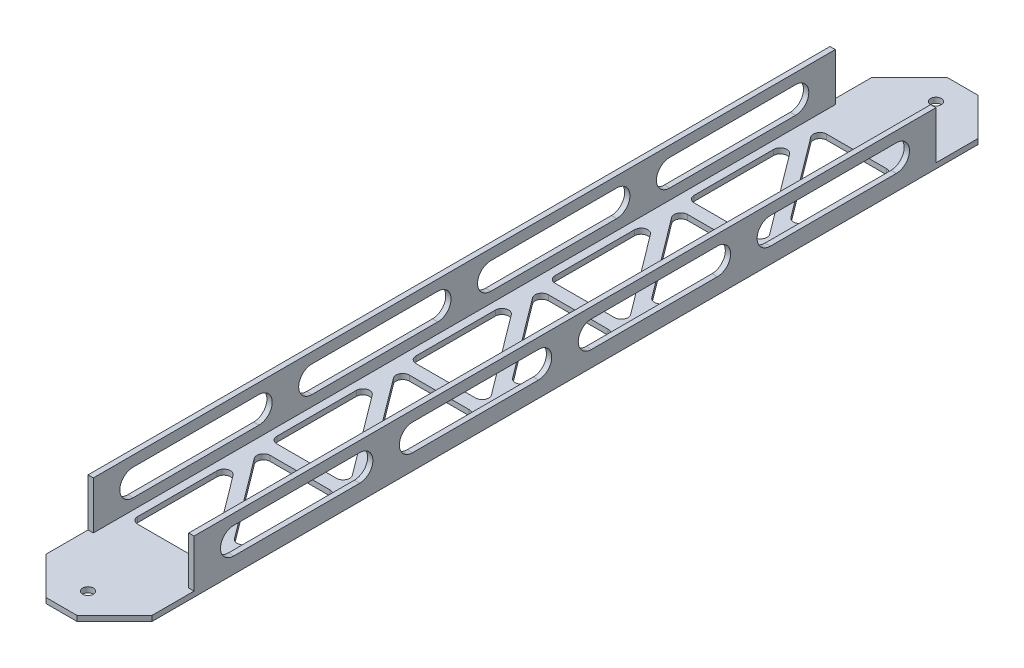
SolidWorks part; units mm, degrees
material "6061 Alloy"
ref_plane "Front" through (0, 0, 0) normal (0, 0, 1) x (1, 0, 0)
ref_plane "Top" through (0, 0, 0) normal (0, 1, 0) x (1, 0, 0)
ref_plane "Right" through (0, 0, 0) normal (1, 0, 0) x (0, 0, -1)
sketch "Sketch1" plane through (0, 0, 0) normal (0, 0, 1) x (1, 0, 0)
  line L0 (48.26, 2.54) -> (48.26, 25.4)
  line L1 (0, 0) -> (50.8, 0)
  line L2 (0, 0) -> (0, 25.4)
  line L4 (50.8, 0) -> (50.8, 25.4)
  line L5 (2.54, 2.54) -> (48.26, 2.54)
  line L6 (2.54, 2.54) -> (2.54, 25.4)
  line L7 (50.8, 25.4) -> (48.26, 25.4)
  line L8 (0, 25.4) -> (2.54, 25.4)
  dimension "D1" = 25.4
  dimension "D2" = 50.8
  dimension "D3" = 2.54
extrude "Boss-Extrude1" add sketch "Sketch1" along normal blind 431.8
sketch "Sketch2" plane through (0, 25.4, 0) normal (0, 1, 0) x (1, 0, 0)
  line L0 (50.8, -431.8) -> (50.8, 0) construction
  line L1 (0, -431.8) -> (50.8, -431.8)
  line L2 (0, -431.8) -> (0, -393.7)
  line L3 (0, -393.7) -> (50.8, -393.7)
  line L4 (50.8, -431.8) -> (50.8, -393.7)
  line L5 (0, -431.8) -> (50.8, -393.7) construction
  line L6 (0, -393.7) -> (50.8, -431.8) construction
  line L7 (0, -215.9) -> (50.8, -215.9) construction
  line L8 (0, -431.8) -> (0, 0) construction
  line L9 (0, -38.1) -> (50.8, 0) construction
  line L10 (0, 0) -> (50.8, -38.1) construction
  line L11 (50.8, 0) -> (50.8, -38.1)
  line L12 (0, -38.1) -> (50.8, -38.1)
  line L13 (0, 0) -> (0, -38.1)
  line L14 (0, 0) -> (50.8, 0)
  point P4 (25.4, -412.75)
  point P16 (25.4, -19.05)
  dimension "D1" = 38.1
extrude "Tabs" cut sketch "Sketch2" against normal up to surface (22.86 mm away) up to face at (25.4, 2.54, 215.9)
sketch "Sketch3" plane through (0, 2.54, 0) normal (0, 1, 0) x (1, 0, 0)
  line L0 (25.4, -431.8) -> (25.4, -419.1) construction
  line L1 (50.8, -431.8) -> (0, -431.8) construction
  line L2 (25.4, 0) -> (25.4, -12.7) construction
  line L3 (50.8, 0) -> (0, 0) construction
  circle A0 centre (25.4, -419.1) radius 2.5797
  circle A1 centre (25.4, -12.7) radius 2.5797
  dimension "D2" = 5.1594
  dimension "D1" = 12.7
extrude "Holes" cut sketch "Sketch3" against normal up to next
sketch "Sketch4" plane through (50.8, 0, 0) normal (1, 0, 0) x (0, 0, -1)
  line L0 (-57.15, 13.97) -> (-117.475, 13.97) construction
  line L1 (-57.15, 7.62) -> (-117.475, 7.62)
  line L2 (-57.15, 20.32) -> (-117.475, 20.32)
  line L3 (-38.1, 13.97) -> (-57.15, 13.97) construction
  line L4 (-38.1, 2.54) -> (-38.1, 25.4) construction
  line L5 (-142.875, 13.97) -> (-203.2, 13.97) construction
  line L6 (-142.875, 7.62) -> (-203.2, 7.62)
  line L7 (-142.875, 20.32) -> (-203.2, 20.32)
  line L8 (-228.6, 13.97) -> (-288.925, 13.97) construction
  line L9 (-228.6, 7.62) -> (-288.925, 7.62)
  line L10 (-228.6, 20.32) -> (-288.925, 20.32)
  line L11 (-314.325, 13.97) -> (-374.65, 13.97) construction
  line L12 (-314.325, 7.62) -> (-374.65, 7.62)
  line L13 (-314.325, 20.32) -> (-374.65, 20.32)
  line L14 (-393.7, 2.54) -> (-393.7, 25.4) construction
  arc A0 (-57.15, 7.62) -> (-57.15, 20.32) centre (-57.15, 13.97) ccw
  arc A1 (-117.475, 20.32) -> (-117.475, 7.62) centre (-117.475, 13.97) ccw
  arc A2 (-142.875, 7.62) -> (-142.875, 20.32) centre (-142.875, 13.97) ccw
  arc A3 (-203.2, 20.32) -> (-203.2, 7.62) centre (-203.2, 13.97) ccw
  arc A4 (-228.6, 7.62) -> (-228.6, 20.32) centre (-228.6, 13.97) ccw
  arc A5 (-288.925, 20.32) -> (-288.925, 7.62) centre (-288.925, 13.97) ccw
  arc A6 (-314.325, 7.62) -> (-314.325, 20.32) centre (-314.325, 13.97) ccw
  arc A7 (-374.65, 20.32) -> (-374.65, 7.62) centre (-374.65, 13.97) ccw
  point P2 (-87.3125, 13.97)
  point P14 (-173.0375, 13.97)
  point P21 (-258.7625, 13.97)
  point P28 (-344.4875, 13.97)
  dimension "D1" = 12.7
  dimension "D2" = 60.325
  dimension "D3" = 19.05
  dimension "D5" = 25.4
  dimension "D6" = 19.05
  dimension "D4" = 4
extrude "Slots" cut sketch "Sketch4" against normal through all
sketch "Sketch5" plane through (0, 0, 0) normal (0, -1, 0) x (1, 0, 0)
  line L0 (44.45, 135.8834) -> (50.8, 135.8834) construction
  line L7 (44.45, 69.2084) -> (50.8, 69.2084) construction
  line L8 (50.8, 431.8) -> (50.8, 0) construction
  line L11 (44.45, 202.5584) -> (50.8, 202.5584) construction
  line L12 (44.45, 269.2334) -> (50.8, 269.2334) construction
  line L13 (44.45, 335.9084) -> (50.8, 335.9084) construction
  line L14 (0, 0) -> (50.8, 0) construction
  point P2 (44.45, 169.8625)
  point P5 (44.45, 103.1875)
  point P7 (44.45, 119.0625)
  point P11 (44.45, 236.5375)
  point P14 (44.45, 185.7375)
  point P15 (44.45, 52.3875)
  point P16 (44.45, 303.2125)
  point P19 (44.45, 252.4125)
  point P20 (44.45, 369.8875)
  point P23 (44.45, 319.0875)
  line B0 (6.35, 52.3875) -> (0, 52.3875) construction
  line B1 (41.275, 52.3875) -> (12.7, 52.3875)
  line B2 (44.45, 55.5625) -> (44.45, 93.6625)
  line B3 (38.735, 95.5675) -> (10.16, 57.4675)
  arc B4 (44.45, 93.6625) -> (38.735, 95.5675) centre (41.275, 93.6625) ccw
  arc B5 (41.275, 52.3875) -> (44.45, 55.5625) centre (41.275, 55.5625) ccw
  arc B6 (12.7, 52.3875) -> (10.16, 57.4675) centre (12.7, 55.5625) cw
  line B7 (44.45, 112.7125) -> (50.8, 112.7125) construction
  line B8 (9.525, 112.7125) -> (38.1, 112.7125)
  line B9 (6.35, 109.5375) -> (6.35, 71.4375)
  line B10 (12.065, 69.5325) -> (40.64, 107.6325)
  arc B11 (6.35, 71.4375) -> (12.065, 69.5325) centre (9.525, 71.4375) ccw
  arc B12 (9.525, 112.7125) -> (6.35, 109.5375) centre (9.525, 109.5375) ccw
  arc B13 (38.1, 112.7125) -> (40.64, 107.6325) centre (38.1, 109.5375) cw
  line B14 (41.275, 119.0625) -> (12.7, 119.0625)
  line B15 (44.45, 122.2375) -> (44.45, 160.3375)
  line B16 (38.735, 162.2425) -> (10.16, 124.1425)
  arc B17 (44.45, 160.3375) -> (38.735, 162.2425) centre (41.275, 160.3375) ccw
  arc B18 (41.275, 119.0625) -> (44.45, 122.2375) centre (41.275, 122.2375) ccw
  arc B19 (12.7, 119.0625) -> (10.16, 124.1425) centre (12.7, 122.2375) cw
  line B20 (9.525, 179.3875) -> (38.1, 179.3875)
  line B21 (6.35, 176.2125) -> (6.35, 138.1125)
  line B22 (12.065, 136.2075) -> (40.64, 174.3075)
  arc B23 (6.35, 138.1125) -> (12.065, 136.2075) centre (9.525, 138.1125) ccw
  arc B24 (9.525, 179.3875) -> (6.35, 176.2125) centre (9.525, 176.2125) ccw
  arc B25 (38.1, 179.3875) -> (40.64, 174.3075) centre (38.1, 176.2125) cw
  line B26 (41.275, 185.7375) -> (12.7, 185.7375)
  line B27 (44.45, 188.9125) -> (44.45, 227.0125)
  line B28 (38.735, 228.9175) -> (10.16, 190.8175)
  arc B29 (44.45, 227.0125) -> (38.735, 228.9175) centre (41.275, 227.0125) ccw
  arc B30 (41.275, 185.7375) -> (44.45, 188.9125) centre (41.275, 188.9125) ccw
  arc B31 (12.7, 185.7375) -> (10.16, 190.8175) centre (12.7, 188.9125) cw
  line B32 (9.525, 246.0625) -> (38.1, 246.0625)
  line B33 (6.35, 242.8875) -> (6.35, 204.7875)
  line B34 (12.065, 202.8825) -> (40.64, 240.9825)
  arc B35 (6.35, 204.7875) -> (12.065, 202.8825) centre (9.525, 204.7875) ccw
  arc B36 (9.525, 246.0625) -> (6.35, 242.8875) centre (9.525, 242.8875) ccw
  arc B37 (38.1, 246.0625) -> (40.64, 240.9825) centre (38.1, 242.8875) cw
  line B38 (41.275, 252.4125) -> (12.7, 252.4125)
  line B39 (44.45, 255.5875) -> (44.45, 293.6875)
  line B40 (38.735, 295.5925) -> (10.16, 257.4925)
  arc B41 (44.45, 293.6875) -> (38.735, 295.5925) centre (41.275, 293.6875) ccw
  arc B42 (41.275, 252.4125) -> (44.45, 255.5875) centre (41.275, 255.5875) ccw
  arc B43 (12.7, 252.4125) -> (10.16, 257.4925) centre (12.7, 255.5875) cw
  line B44 (9.525, 312.7375) -> (38.1, 312.7375)
  line B45 (6.35, 309.5625) -> (6.35, 271.4625)
  line B46 (12.065, 269.5575) -> (40.64, 307.6575)
  arc B47 (6.35, 271.4625) -> (12.065, 269.5575) centre (9.525, 271.4625) ccw
  arc B48 (9.525, 312.7375) -> (6.35, 309.5625) centre (9.525, 309.5625) ccw
  arc B49 (38.1, 312.7375) -> (40.64, 307.6575) centre (38.1, 309.5625) cw
  line B50 (41.275, 319.0875) -> (12.7, 319.0875)
  line B51 (44.45, 322.2625) -> (44.45, 360.3625)
  line B52 (38.735, 362.2675) -> (10.16, 324.1675)
  arc B53 (44.45, 360.3625) -> (38.735, 362.2675) centre (41.275, 360.3625) ccw
  arc B54 (41.275, 319.0875) -> (44.45, 322.2625) centre (41.275, 322.2625) ccw
  arc B55 (12.7, 319.0875) -> (10.16, 324.1675) centre (12.7, 322.2625) cw
  line B56 (9.525, 379.4125) -> (38.1, 379.4125)
  line B57 (6.35, 376.2375) -> (6.35, 338.1375)
  line B58 (12.065, 336.2325) -> (40.64, 374.3325)
  arc B59 (6.35, 338.1375) -> (12.065, 336.2325) centre (9.525, 338.1375) ccw
  arc B60 (9.525, 379.4125) -> (6.35, 376.2375) centre (9.525, 376.2375) ccw
  arc B61 (38.1, 379.4125) -> (40.64, 374.3325) centre (38.1, 376.2375) cw
  dimension "D3" = 60.325
  dimension "D1" = 50.8
  dimension "D2" = 38.1
  dimension "D4" = 6.35
  dimension "D5" = 52.3875
sketch_block_instance "Block1-1"
sketch_block "Block1" parameters "D1"=3.175
sketch_block_instance "Block1-2"
sketch_block_instance "Block1-4"
sketch_block_instance "Block1-5"
sketch_block_instance "Block1-6"
sketch_block_instance "Block1-7"
sketch_block_instance "Block1-8"
sketch_block_instance "Block1-9"
sketch_block_instance "Block1-10"
sketch_block_instance "Block1-11"
extrude "Trig_Holes" cut sketch "Sketch5" against normal up to next
sketch "Sketch6" plane through (0, 0, 0) normal (0, -1, 0) x (1, 0, 0)
  line L0 (32.8395, 0) -> (50.8, 17.9605)
  line L1 (0, 0) -> (50.8, 0) construction
  line L2 (50.8, 431.8) -> (50.8, 0) construction
  line L3 (25.4, 0) -> (25.4, 5.8117) construction
  line L4 (17.9605, 0) -> (0, 17.9605)
  line L5 (50.8, 215.9) -> (0, 215.9) construction
  line L6 (0, 431.8) -> (0, 0) construction
  line L7 (32.8395, 431.8) -> (50.8, 413.8395)
  line L8 (17.9605, 431.8) -> (0, 413.8395)
  line L9 (0, 17.9605) -> (0, 0)
  line L10 (0, 0) -> (17.9605, 0)
  line L11 (32.8395, 0) -> (50.8, 0)
  line L12 (50.8, 0) -> (50.8, 17.9605)
  line L13 (0, 413.8395) -> (0, 431.8)
  line L14 (0, 431.8) -> (50.8, 431.8) construction
  line L15 (0, 431.8) -> (17.9605, 431.8)
  line L16 (32.8395, 431.8) -> (50.8, 431.8)
  line L17 (50.8, 431.8) -> (50.8, 413.8395)
  dimension "D1" = 25.4
  dimension "D2" = 45
extrude "Tab_Corner_Cuts" cut sketch "Sketch6" against normal up to next
ref_plane "Mid_Plane" through (0, 12.7, 0) normal (0, 1, 0) x (1, 0, 0)
ref_plane "Plane2" through (0, 13.97, 0) normal (0, 1, 0) x (1, 0, 0)
